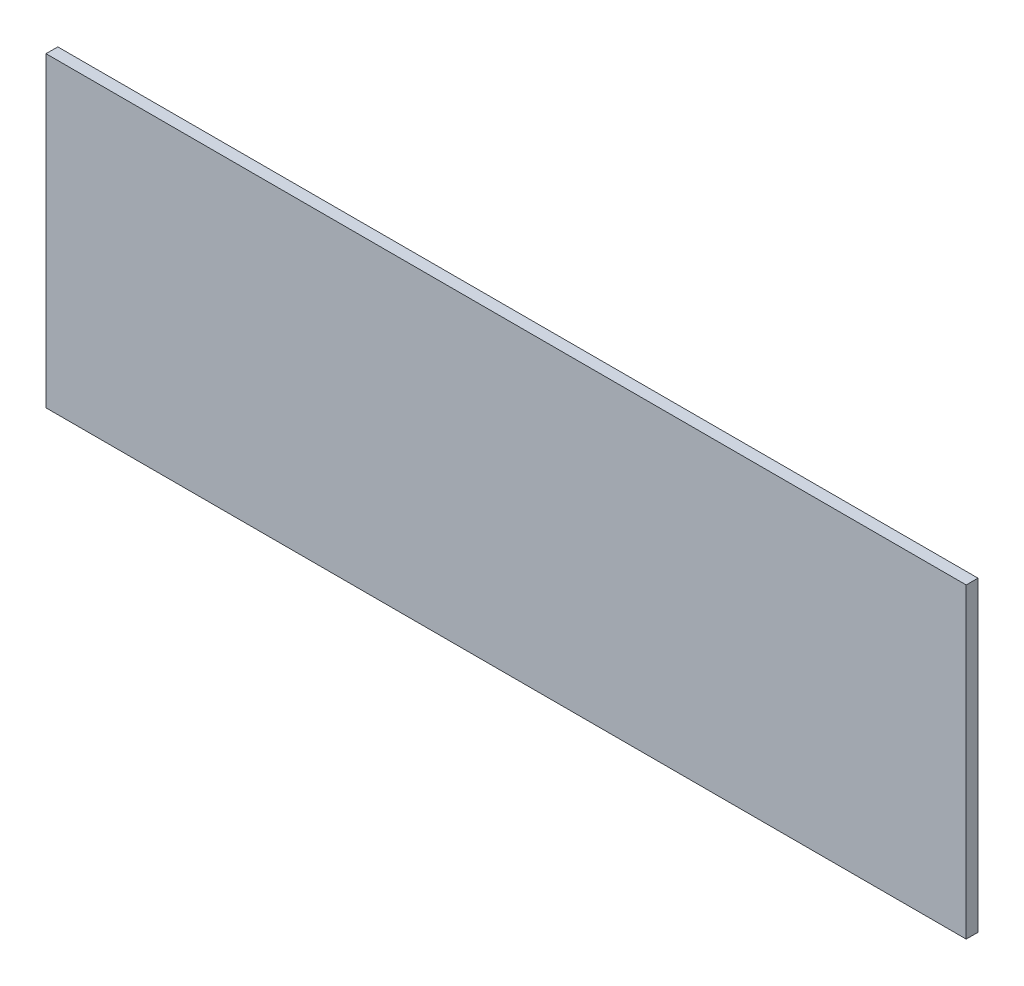
SolidWorks part; units mm, degrees
ref_plane "Front Plane" through (0, 0, 0) normal (0, 0, 1) x (1, 0, 0)
ref_plane "Top Plane" through (0, 0, 0) normal (0, 1, 0) x (1, 0, 0)
ref_plane "Right Plane" through (0, 0, 0) normal (1, 0, 0) x (0, 0, -1)
sketch "Sketch1" plane through (0, 0, 0) normal (0, 0, 1) x (1, 0, 0)
  line L1 (195, -65) -> (-195, -65)
  line L2 (195, -65) -> (195, 65)
  line L3 (195, 65) -> (-195, 65)
  line L4 (-195, -65) -> (-195, 65)
  line L5 (195, -65) -> (-195, 65) construction
  line L6 (195, 65) -> (-195, -65) construction
  point P0 (0, 0)
  dimension "D1" = 390
  dimension "D2" = 130
extrude "Boss-Extrude1" add sketch "Sketch1" along normal mid plane 5
